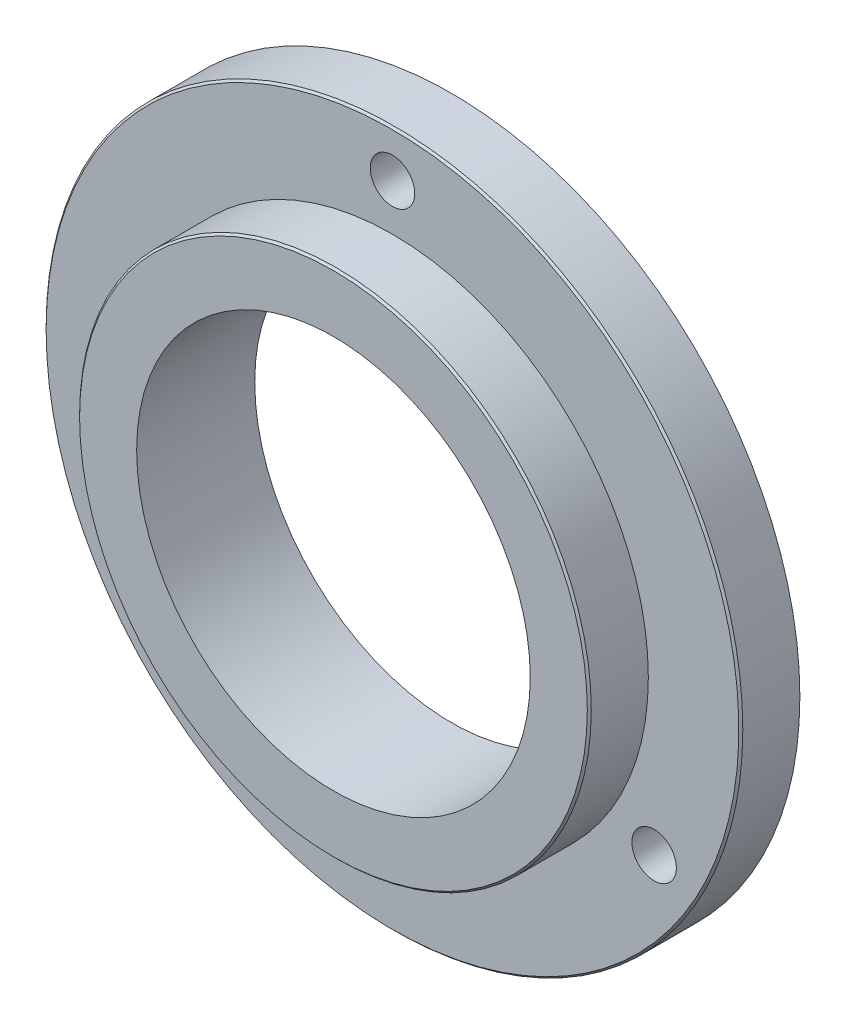
SolidWorks part; units mm, degrees
ref_plane "Plan de face" through (0, 0, 0) normal (0, 0, 1) x (1, 0, 0)
ref_plane "Plan de dessus" through (0, 0, 0) normal (0, 1, 0) x (1, 0, 0)
ref_plane "Plan de droite" through (0, 0, 0) normal (1, 0, 0) x (0, 0, -1)
sketch "Esquisse1" [suppressed] plane through (0, 0, 0) normal (0, 0, 1) x (1, 0, 0)
  circle A0 centre (0, 0) radius 40.8746
sketch "Esquisse10" plane through (0, 0, 0) normal (0, 0, 1) x (1, 0, 0)
  circle A0 centre (0, 0) radius 13
  circle A1 centre (0, 0) radius 10
extrude "Boss.-Extru.2" add sketch "Esquisse10" along normal blind 3
sketch "Esquisse11" plane through (0, 0, 0) normal (0, 0, -1) x (-1, 0, 0)
  circle A0 centre (0, 0) radius 10
  circle A1 centre (0, 0) radius 17.7
extrude "Boss.-Extru.3" add sketch "Esquisse11" along normal blind 3
sketch "Sketch4" plane through (0, 0, 0) normal (0, 0, 1) x (1, 0, 0)
  line L0 (0, 17.7) -> (0, 13)
  circle A0 centre (0, 0) radius 17.7 construction
  circle A1 centre (0, 0) radius 13 construction
hole_wizard "#4-40 Tapped Hole1" positions "Sketch5" profile "Sketch6" tap size "#4-40" standard "ANSI Inch" end condition through all
sketch "Sketch5" plane through (0, 0, 0) normal (0, 0, 1) x (1, 0, 0)
  line L0 (0, 17.7) -> (0, 13) construction
  point P0 (0, 15.35)
sketch "Sketch6" plane through (0, 15.35, 0) normal (1, 0, 0) x (0, -1, 0)
  line L0 (0, 0) -> (0, 3)
  line L1 (0, 3) -> (1.1303, 3)
  line L2 (1.1303, 3) -> (1.1303, 0)
  line L5 (1.1303, 0) -> (0, 0)
  line L11 (0, -6.35) -> (0, 107.95) construction
  dimension "Thru Tap Drill Dia." = 2.2606
  dimension "Thru Tap Drill Depth" = 3
pattern_circular "CirPattern1" count 3 over 360 about axis through (0, 0, 3) along (0, 0, -1) of "#4-40 Tapped Hole1"
chamfer "Chamfer1" distance 0.1 angle 45 1 edges at (-17.7, 0, 0)
chamfer "Chamfer2" distance 0.1 angle 45 1 edges at (13, 0, 3)
